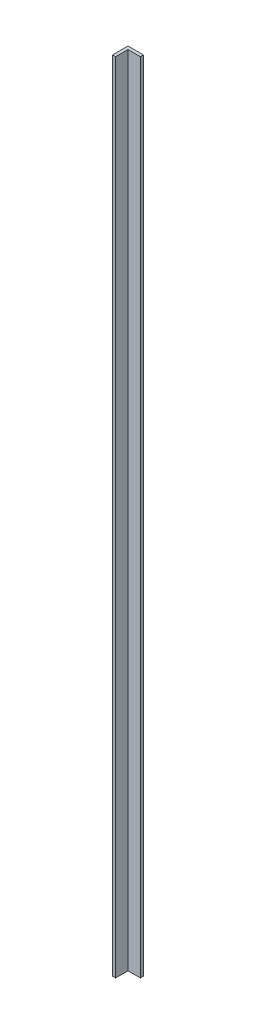
SolidWorks part; units mm, degrees
ref_plane "Front Plane" through (0, 0, 0) normal (0, 0, 1) x (1, 0, 0)
ref_plane "Top Plane" through (0, 0, 0) normal (0, 1, 0) x (1, 0, 0)
ref_plane "Right Plane" through (0, 0, 0) normal (1, 0, 0) x (0, 0, -1)
sketch "Sketch1" plane through (0, 0, 0) normal (0, 1, 0) x (1, 0, 0)
  line L0 (0, 0) -> (6.5, 0)
  line L1 (0, 0) -> (0, -6.5)
  line L4 (-1.5875, 1.5875) -> (6.5, 1.5875)
  line L5 (-1.5875, 1.5875) -> (-1.5875, -6.5)
  line L9 (-1.5875, -6.5) -> (0, -6.5)
  line L10 (6.5, 0) -> (6.5, 1.5875)
  dimension "D1" = 6.5
  dimension "D2" = 6.5
  dimension "D3" = 1.5875
extrude "Boss-Extrude1" add sketch "Sketch1" along normal blind 417.068
